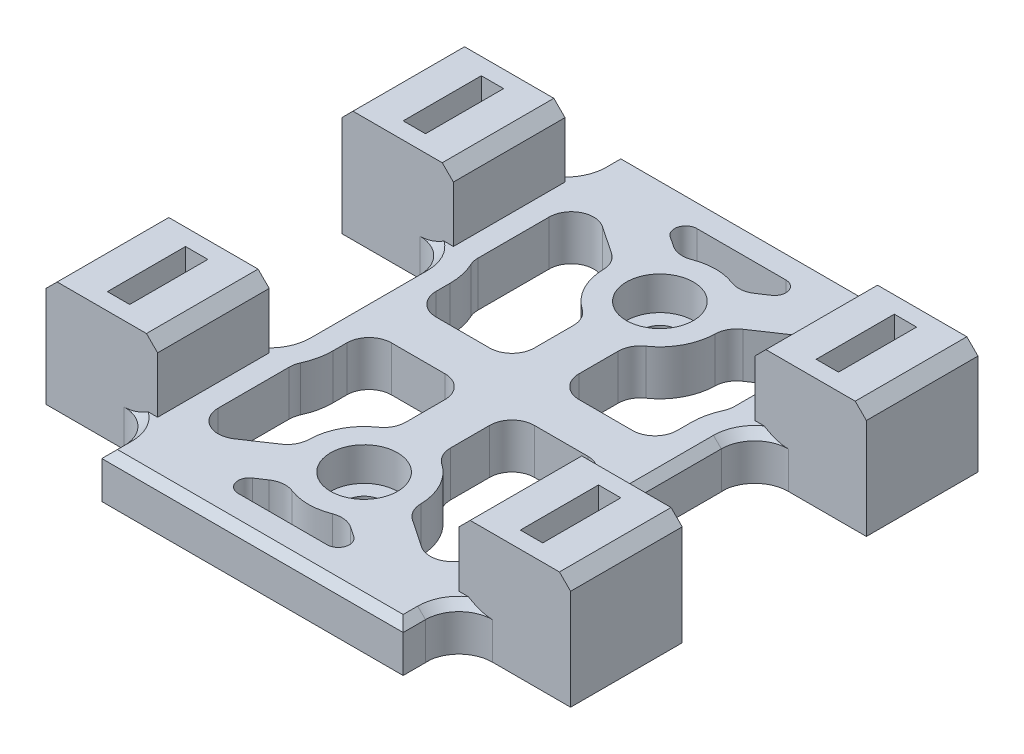
SolidWorks part; units mm, degrees
material "Thornel Mat VMA"
ref_plane "Front Plane" through (0, 0, 0) normal (0, 0, 1) x (1, 0, 0)
ref_plane "Top Plane" through (0, 0, 0) normal (0, 1, 0) x (1, 0, 0)
ref_plane "Right Plane" through (0, 0, 0) normal (1, 0, 0) x (0, 0, -1)
sketch "Sketch1" plane through (0, 0, 0) normal (0, 1, 0) x (1, 0, 0)
  line L1 (-13.5, -24.7597) -> (13.5, -24.7597)
  line L2 (-13.5, -24.7597) -> (-13.5, 21.7403)
  line L3 (-13.5, 21.7403) -> (13.5, 21.7403)
  line L4 (13.5, -24.7597) -> (13.5, 21.7403)
  line L5 (-13.5, -24.7597) -> (13.5, 21.7403) construction
  line L6 (-13.5, 21.7403) -> (13.5, -24.7597) construction
  point P0 (0, -1.5097)
  dimension "D1" = 27
  dimension "D2" = 46.5
extrude "Boss-Extrude1" add sketch "Sketch1" along normal blind 4 and the other way blind 0.0388
sketch "Sketch2" plane through (0, 0, 0) normal (0, 1, 0) x (1, 0, 0)
  line L0 (-13.5, 21.7403) -> (-13.5, -24.7597) construction
  line L1 (-13.5, 16.7403) -> (-23.5, 16.7403)
  line L2 (-13.5, 16.7403) -> (-13.5, 6.7403)
  line L3 (-13.5, 6.7403) -> (-23.5, 6.7403)
  line L4 (-23.5, 16.7403) -> (-23.5, 6.7403)
  line L5 (13.5, 21.7403) -> (-13.5, 21.7403) construction
  line L6 (-15, 15.2403) -> (-22, 15.2403)
  line L7 (-22, 15.2403) -> (-22, 8.2403)
  line L8 (-15, 8.2403) -> (-22, 8.2403)
  line L9 (-15, 15.2403) -> (-15, 8.2403)
  line L10 (13.5, -19.7597) -> (23.5, -19.7597)
  line L12 (15, 15.2403) -> (15, 8.2403)
  line L13 (15, 8.2403) -> (22, 8.2403)
  line L14 (22, 15.2403) -> (22, 8.2403)
  line L15 (15, 15.2403) -> (22, 15.2403)
  line L16 (23.5, 16.7403) -> (23.5, 6.7403)
  line L17 (13.5, 6.7403) -> (23.5, 6.7403)
  line L18 (13.5, 16.7403) -> (13.5, 6.7403)
  line L19 (13.5, 16.7403) -> (23.5, 16.7403)
  line L20 (13.5, -19.7597) -> (13.5, -9.7597)
  line L21 (13.5, -9.7597) -> (23.5, -9.7597)
  line L22 (23.5, -19.7597) -> (23.5, -9.7597)
  line L23 (15, -18.2597) -> (22, -18.2597)
  line L24 (22, -18.2597) -> (22, -11.2597)
  line L25 (15, -11.2597) -> (22, -11.2597)
  line L26 (15, -18.2597) -> (15, -11.2597)
  line L27 (-15, -18.2597) -> (-15, -11.2597)
  line L28 (-15, -11.2597) -> (-22, -11.2597)
  line L29 (-22, -18.2597) -> (-22, -11.2597)
  line L30 (-15, -18.2597) -> (-22, -18.2597)
  line L31 (-23.5, -19.7597) -> (-23.5, -9.7597)
  line L32 (-13.5, -9.7597) -> (-23.5, -9.7597)
  line L33 (-13.5, -19.7597) -> (-13.5, -9.7597)
  line L34 (-13.5, -19.7597) -> (-23.5, -19.7597)
  dimension "D1" = 10
  dimension "D2" = 10
  dimension "D3" = 5
  dimension "D4" = 1.5
extrude "Boss-Extrude2" add sketch "Sketch2" along normal blind 7
fillet "Fillet1" radius 3 8 edges at (-13.5, 2, 19.7597) (-13.5, 2, -6.7403) (-13.5, 2, -16.7403) (-13.5, 2, 9.7597) (13.5, 2, -16.7403) (13.5, 2, 9.7597) (13.5, 2, -6.7403) (13.5, 2, 19.7597)
chamfer "Chamfer1" distance 0.7 angle 45 16 edges at (-13.5, 4, 23.7597) (-14.3787, 4, 20.6384) (13.5, 4, 23.7597) (14.3787, 4, 20.6384) (0, 4, 24.7597) (-14.3787, 4, -5.8616) (-14.3787, 4, 8.8811) (-13.5, 4, 1.5097) (14.3787, 4, 8.8811) (14.3787, 4, -5.8616) (13.5, 4, 1.5097) (13.5, 4, -20.7403) (14.3787, 4, -17.6189) (-13.5, 4, -20.7403) (-14.3787, 4, -17.6189) (0, 4, -21.7403)
sketch "Sketch3" plane through (0, 7, 0) normal (0, 1, 0) x (1, 0, 0)
  line L0 (-15, 15.2403) -> (-22, 15.2403) construction
  line L1 (-23.5, 16.7403) -> (-13.5, 16.7403)
  line L2 (-23.5, 16.7403) -> (-23.5, 6.7403)
  line L3 (-23.5, 6.7403) -> (-13.5, 6.7403)
  line L4 (-13.5, 16.7403) -> (-13.5, 6.7403)
  line L5 (-19.5, 15.2403) -> (-17.5, 15.2403)
  line L6 (-19.5, 15.2403) -> (-19.5, 8.2403)
  line L7 (-19.5, 8.2403) -> (-17.5, 8.2403)
  line L8 (-17.5, 15.2403) -> (-17.5, 8.2403)
  line L9 (-22, 8.2403) -> (-15, 8.2403) construction
  line L10 (23.5, -19.7597) -> (13.5, -19.7597)
  line L13 (17.5, 15.2403) -> (17.5, 8.2403)
  line L14 (19.5, 8.2403) -> (17.5, 8.2403)
  line L15 (19.5, 15.2403) -> (19.5, 8.2403)
  line L16 (19.5, 15.2403) -> (17.5, 15.2403)
  line L17 (13.5, 16.7403) -> (13.5, 6.7403)
  line L18 (23.5, 6.7403) -> (13.5, 6.7403)
  line L19 (23.5, 16.7403) -> (23.5, 6.7403)
  line L20 (23.5, 16.7403) -> (13.5, 16.7403)
  line L21 (23.5, -19.7597) -> (23.5, -9.7597)
  line L22 (23.5, -9.7597) -> (13.5, -9.7597)
  line L23 (13.5, -19.7597) -> (13.5, -9.7597)
  line L24 (19.5, -18.2597) -> (17.5, -18.2597)
  line L25 (19.5, -18.2597) -> (19.5, -11.2597)
  line L26 (19.5, -11.2597) -> (17.5, -11.2597)
  line L27 (17.5, -18.2597) -> (17.5, -11.2597)
  line L28 (-17.5, -18.2597) -> (-17.5, -11.2597)
  line L29 (-19.5, -11.2597) -> (-17.5, -11.2597)
  line L30 (-19.5, -18.2597) -> (-19.5, -11.2597)
  line L31 (-19.5, -18.2597) -> (-17.5, -18.2597)
  line L32 (-13.5, -19.7597) -> (-13.5, -9.7597)
  line L33 (-23.5, -9.7597) -> (-13.5, -9.7597)
  line L34 (-23.5, -19.7597) -> (-23.5, -9.7597)
  line L35 (-23.5, -19.7597) -> (-13.5, -19.7597)
  dimension "D1" = 2
  dimension "D2" = 4
  dimension "D3" = 4
extrude "Boss-Extrude3" add sketch "Sketch3" along normal blind 3
chamfer "Chamfer3" distance 1 angle 45 8 edges at (-23.5, 10, 14.7597) (-23.5, 10, -11.7403) (-13.5, 10, -11.7403) (-13.5, 10, 14.7597) (23.5, 10, -11.7403) (23.5, 10, 14.7597) (13.5, 10, 14.7597) (13.5, 10, -11.7403)
sketch "Sketch4" plane through (0, 4, 0) normal (0, 1, 0) x (1, 0, 0)
  circle A0 centre (0, 11.7403) radius 3
  circle A1 centre (0, -14.7597) radius 3
  dimension "D1" = 6
extrude "Cut-Extrude1" cut sketch "Sketch4" against normal blind 3
sketch "Sketch5" plane through (0, 1, 0) normal (0, 1, 0) x (1, 0, 0)
  circle A0 centre (0, -14.7597) radius 1.6
  circle A1 centre (0, 11.7403) radius 1.6
extrude "Cut-Extrude2" cut sketch "Sketch5" against normal blind 3
sketch "Sketch6" plane through (0, 4, 0) normal (0, 1, 0) x (1, 0, 0)
  line L0 (-2, 2.4903) -> (-2, 5.9957)
  line L1 (10.8, 2.4903) -> (10.8, 3.7403)
  line L2 (4, -3.5097) -> (8.8, -3.5097)
  line L3 (-4, 0.4903) -> (-8.8, 0.4903)
  line L4 (4, 0.4903) -> (8.8, 0.4903)
  line L5 (-4, -3.5097) -> (-8.8, -3.5097)
  line L6 (-10.8, -5.5097) -> (-10.8, -6.7597)
  line L7 (2, 2.4903) -> (2, 5.9957)
  line L21 (2, -9.0152) -> (2, -5.5097)
  line L22 (-2, -9.0152) -> (-2, -5.5097)
  line L26 (3.6483, 16.6075) -> (4.5444, 17.2107)
  line L27 (-3.6483, 16.6075) -> (-4.5444, 17.2107)
  line L28 (-4.5444, -20.2302) -> (-3.6483, -19.6269)
  line L29 (3.6483, -19.6269) -> (4.5444, -20.2302)
  line L30 (5.8822, 13.2894) -> (8.3831, 14.973)
  line L31 (-5.8822, 13.2894) -> (-8.3831, 14.973)
  line L32 (-8.3831, -17.9925) -> (-5.8822, -16.3088)
  line L33 (5.8822, -16.3088) -> (8.3831, -17.9925)
  line L40 (-10.8431, -22.0597) -> (10.8431, -22.0597)
  line L41 (11.5, -20.023) -> (11.5, -9.4965)
  line L42 (10.8, -6.7597) -> (10.8, 3.7403)
  line L43 (11.5, 6.477) -> (11.5, 17.0035)
  line L44 (10.8431, 19.0403) -> (-10.8431, 19.0403)
  line L45 (-11.5, 17.0035) -> (-11.5, 6.477)
  line L46 (-10.8, 3.7403) -> (-10.8, -6.7597)
  line L47 (-11.5, -9.4965) -> (-11.5, -20.023)
  line L48 (-3.9859, -22.0597) -> (3.9859, -22.0597)
  line L49 (11.5, -16.3335) -> (11.5, -9.9675)
  line L50 (10.8, -6.7597) -> (10.8, -5.5097)
  line L51 (11.5, 6.9481) -> (11.5, 13.314)
  line L52 (3.9859, 19.0403) -> (-3.9859, 19.0403)
  line L53 (-11.5, 13.314) -> (-11.5, 6.9481)
  line L54 (-10.8, 3.7403) -> (-10.8, 2.4903)
  line L55 (-11.5, -9.9675) -> (-11.5, -16.3335)
  arc A0 (-4.9994, 11.6617) -> (-2.8571, 7.637) centre (0, 11.7403) ccw
  arc A1 (1.8081, 16.4019) -> (-1.8081, 16.4019) centre (0, 11.7403) ccw
  arc A2 (3.6483, -19.6269) -> (1.8081, -19.4214) centre (2.5314, -21.286) ccw
  arc A3 (-1.8081, -19.4214) -> (-3.6483, -19.6269) centre (-2.5314, -21.286) ccw
  arc A4 (8.8, -3.5097) -> (10.8, -5.5097) centre (8.8, -5.5097) cw
  arc A5 (11.5, -9.9675) -> (11.3182, -9.1343) centre (9.5, -9.9675) ccw
  arc A6 (2, -9.0152) -> (2.8571, -10.6565) centre (4, -9.0152) ccw
  arc A7 (5.8822, -16.3088) -> (4.9994, -14.6812) centre (6.9991, -14.6498) cw
  arc A8 (-4.9994, -14.6812) -> (-5.8822, -16.3088) centre (-6.9991, -14.6498) cw
  arc A9 (-2, -9.0152) -> (-2.8571, -10.6565) centre (-4, -9.0152) cw
  circle A10 centre (0, 11.7403) radius 5
  arc A11 (2.8571, 7.637) -> (4.9994, 11.6617) centre (0, 11.7403) ccw
  arc A12 (-1.8081, -19.4214) -> (1.8081, -19.4214) centre (0, -14.7597) ccw
  circle A13 centre (0, -14.7597) radius 5
  arc A14 (-2.8571, -10.6565) -> (-4.9994, -14.6812) centre (0, -14.7597) ccw
  arc A15 (4.9994, -14.6812) -> (2.8571, -10.6565) centre (0, -14.7597) ccw
  arc A16 (-10.8431, -22.0597) -> (-11.5, -20.023) centre (-16.5, -22.7597) ccw
  arc A17 (11.5, -20.023) -> (10.8431, -22.0597) centre (16.5, -22.7597) ccw
  arc A18 (10.8, -6.7597) -> (11.5, -9.4965) centre (16.5, -6.7597) ccw
  arc A19 (11.5, 6.477) -> (10.8, 3.7403) centre (16.5, 3.7403) ccw
  arc A20 (10.8431, 19.0403) -> (11.5, 17.0035) centre (16.5, 19.7403) ccw
  arc A21 (-11.5, 17.0035) -> (-10.8431, 19.0403) centre (-16.5, 19.7403) ccw
  arc A22 (-10.8, 3.7403) -> (-11.5, 6.477) centre (-16.5, 3.7403) ccw
  arc A23 (-11.5, -9.4965) -> (-10.8, -6.7597) centre (-16.5, -6.7597) ccw
  arc A26 (10.8, -6.7597) -> (11.3182, -9.1343) centre (16.5, -6.7597) ccw
  arc A27 (11.3182, 6.1149) -> (10.8, 3.7403) centre (16.5, 3.7403) ccw
  arc A30 (-10.8, 3.7403) -> (-11.3182, 6.1149) centre (-16.5, 3.7403) ccw
  arc A31 (-11.3182, -9.1343) -> (-10.8, -6.7597) centre (-16.5, -6.7597) ccw
  arc A32 (-11.3182, -9.1343) -> (-11.5, -9.9675) centre (-9.5, -9.9675) ccw
  arc A33 (-8.8, -3.5097) -> (-10.8, -5.5097) centre (-8.8, -5.5097) ccw
  arc A34 (-4, -3.5097) -> (-2, -5.5097) centre (-4, -5.5097) cw
  arc A35 (4, -3.5097) -> (2, -5.5097) centre (4, -5.5097) ccw
  arc A36 (3.6483, 16.6075) -> (1.8081, 16.4019) centre (2.5314, 18.2665) cw
  arc A37 (-3.6483, 16.6075) -> (-1.8081, 16.4019) centre (-2.5314, 18.2665) ccw
  arc A38 (11.3182, 6.1149) -> (11.5, 6.9481) centre (9.5, 6.9481) ccw
  arc A39 (8.8, 0.4903) -> (10.8, 2.4903) centre (8.8, 2.4903) ccw
  arc A40 (2, 5.9957) -> (2.8571, 7.637) centre (4, 5.9957) cw
  arc A41 (4, 0.4903) -> (2, 2.4903) centre (4, 2.4903) cw
  arc A42 (-4, 0.4903) -> (-2, 2.4903) centre (-4, 2.4903) ccw
  arc A43 (-2, 5.9957) -> (-2.8571, 7.637) centre (-4, 5.9957) ccw
  arc A44 (-11.5, 6.9481) -> (-11.3182, 6.1149) centre (-9.5, 6.9481) ccw
  arc A45 (-8.8, 0.4903) -> (-10.8, 2.4903) centre (-8.8, 2.4903) cw
  arc A46 (3.9859, -22.0597) -> (4.5444, -20.2302) centre (3.9859, -21.0597) ccw
  arc A47 (-4.5444, -20.2302) -> (-3.9859, -22.0597) centre (-3.9859, -21.0597) ccw
  arc A48 (-3.9859, 19.0403) -> (-4.5444, 17.2107) centre (-3.9859, 18.0403) ccw
  arc A49 (3.9859, 19.0403) -> (4.5444, 17.2107) centre (3.9859, 18.0403) cw
  arc A50 (-5.8822, 13.2894) -> (-4.9994, 11.6617) centre (-6.9991, 11.6303) cw
  arc A51 (5.8822, 13.2894) -> (4.9994, 11.6617) centre (6.9991, 11.6303) ccw
  arc A52 (11.5, 13.314) -> (8.3831, 14.973) centre (9.5, 13.314) ccw
  arc A53 (-11.5, 13.314) -> (-8.3831, 14.973) centre (-9.5, 13.314) cw
  arc A54 (-8.3831, -17.9925) -> (-11.5, -16.3335) centre (-9.5, -16.3335) cw
  arc A55 (11.5, -16.3335) -> (8.3831, -17.9925) centre (9.5, -16.3335) cw
  point P53 (4.9183, -15.6599)
  point P79 (2.6844, 15.9585)
  point P116 (-4.9183, 12.6404)
  dimension "D4" = 2
  dimension "D5" = 1
  dimension "D6" = 2
  dimension "D7" = 2
  dimension "D1" = 2
  dimension "D2" = 2
  dimension "D3" = 2
extrude "Cut-Extrude3" cut sketch "Sketch6" against normal through all both and the other way through all
